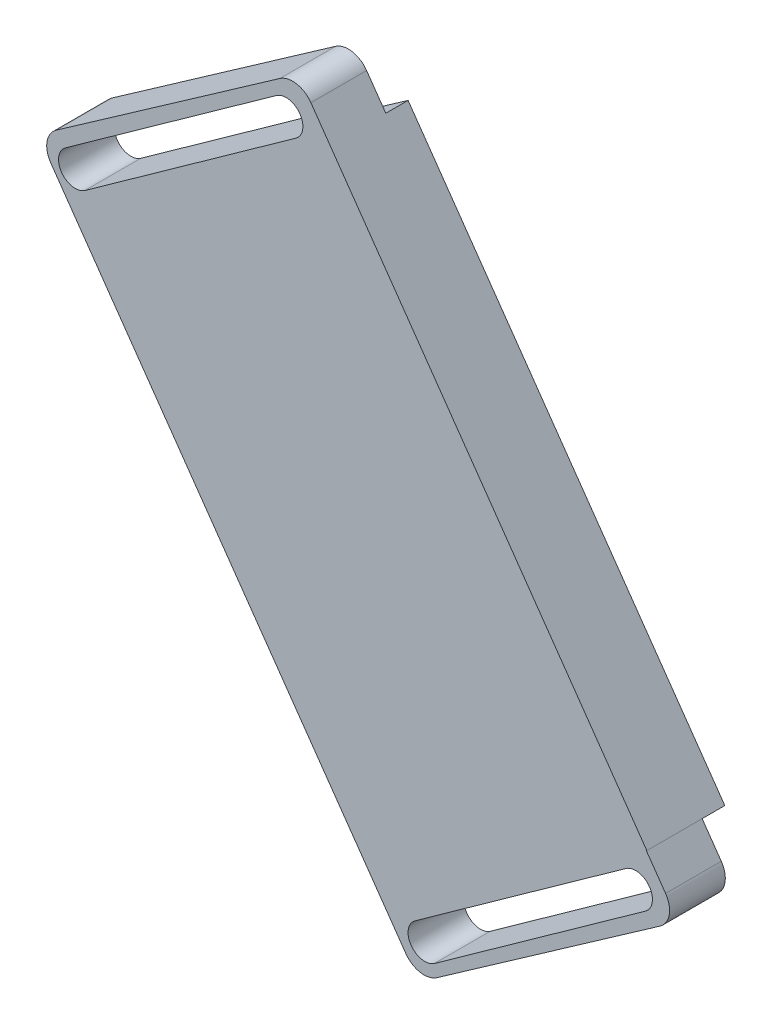
SolidWorks part; units mm, degrees
ref_plane "Piano frontale" through (0, 0, 0) normal (0, 0, 1) x (1, 0, 0)
ref_plane "Piano superiore" through (0, 0, 0) normal (0, 1, 0) x (1, 0, 0)
ref_plane "Piano destro" through (0, 0, 0) normal (1, 0, 0) x (0, 0, -1)
sketch "Schizzo1" plane through (0, 0, 0) normal (0, 0, 1) x (1, 0, 0)
  line L0 (-15.9091, 13.6426) -> (-5.6697, 20.8123)
  line L1 (-15.9091, 13.6426) -> (12.5116, -26.9464)
  line L2 (12.5116, -26.9464) -> (22.751, -19.7767)
  line L3 (-5.6697, 20.8123) -> (22.751, -19.7767)
  line L4 (-15.9091, 13.6426) -> (22.751, -19.7767) construction
  line L5 (12.5116, -26.9464) -> (-5.6697, 20.8123) construction
  line L6 (-6.5469, 19.0139) -> (20.7611, -19.9859)
  line L7 (-6.5469, 19.0139) -> (-13.9192, 13.8518)
  line L8 (-13.9192, 13.8518) -> (13.3888, -25.1481)
  line L9 (20.7611, -19.9859) -> (13.3888, -25.1481)
  line L10 (-6.5469, 19.0139) -> (13.3888, -25.1481) construction
  line L11 (-13.9192, 13.8518) -> (20.7611, -19.9859) construction
  line L12 (13.3888, -25.1481) -> (20.7611, -19.9859)
  line L13 (13.3888, -25.1481) -> (-13.9192, 13.8518)
  line L14 (20.7611, -19.9859) -> (-6.5469, 19.0139)
  line L15 (-13.9192, 13.8518) -> (-6.5469, 19.0139)
  line L16 (13.2898, -26.2909) -> (13.2041, -26.1685)
  line L17 (-15.1309, 14.2981) -> (-14.9919, 14.0995)
  line L18 (-14.9919, 14.0995) -> (-15.811, 13.526)
  line L19 (13.2041, -26.1685) -> (12.385, -26.7421)
  line L20 (-14.9919, 14.0995) -> (13.2041, -26.1685)
  line L21 (-14.9919, 14.0995) -> (-14.5004, 14.4437)
  line L22 (13.2041, -26.1685) -> (13.6956, -25.8244)
  line L23 (-14.5004, 14.4437) -> (13.6956, -25.8244)
  line L24 (-6.5298, 20.3206) -> (-6.3667, 20.0876)
  line L26 (21.8909, -20.2683) -> (21.7964, -20.1334)
  line L27 (21.7964, -20.1334) -> (22.6155, -19.5598)
  line L28 (-6.3667, 20.0876) -> (21.7964, -20.1334)
  line L29 (-6.3667, 20.0876) -> (-6.8582, 19.7435)
  line L30 (21.7964, -20.1334) -> (21.3049, -20.4775)
  line L31 (-6.8582, 19.7435) -> (21.3049, -20.4775)
  point P4 (0, 0)
  point P5 (3.421, -3.0671)
  point P10 (0, 0)
  point P11 (0, 0)
extrude "Estrusione-Estrusione1" add sketch "Schizzo1" along normal blind 7 contours L0 L3 L2 L1
extrude "Taglio-Estrusione1" cut sketch "Schizzo1<3>" along normal blind 6 contours L23 L21 L20 L22 | L29 L31 L30 L28 region at (-0.6481, -5.8624, 0) region at (7.4691, -0.195, 0)
sketch "Schizzo1<3>" plane through (0, 0, 0) normal (0, 0, 1) x (1, 0, 0) same geometry as "Schizzo1"
sketch "Schizzo3" plane through (16.7769, -23.9598, 0) normal (0.5736, -0.8192, 0) x (-0.8192, -0.5736, 0)
  line L1 (-7.2931, -7) -> (-23.2931, -7)
  line L2 (-7.2931, -7) -> (-7.2931, 0)
  line L3 (-7.2931, 0) -> (-23.2931, 0)
  line L4 (-23.2931, -7) -> (-23.2931, 0)
  line L5 (-7.2931, -7) -> (-23.2931, 0) construction
  line L6 (-7.2931, 0) -> (-23.2931, -7) construction
  point P4 (-15.2931, -3.5)
extrude "Estrusione-Estrusione2" add sketch "Schizzo3" against normal up to vertex (49.55 mm away) up to point (-5.6697, 20.8123, 7)
sketch "Schizzo6" plane through (16.7769, -23.9598, 0) normal (0.5736, -0.8192, 0) x (-0.8192, -0.5736, 0)
  line L1 (5.2069, -7) -> (-23.2458, -7)
  line L3 (5.2069, -2) -> (-23.2458, -2)
  line L5 (-23.2458, -2) -> (-23.2458, -7)
  line L6 (5.2069, -2) -> (5.2069, -7)
extrude "Estrusione-Estrusione5" add sketch "Schizzo6" along normal blind 5
sketch "Schizzo7" plane through (-11.6439, 16.6291, 0) normal (-0.5736, 0.8192, 0) x (0.8192, 0.5736, 0)
  line L0 (23.2931, 0) -> (23.2931, -7) construction
  line L1 (-5.2069, -7) -> (23.2931, -7)
  line L3 (-5.2069, -2) -> (23.2931, -2)
  line L5 (23.2931, -2) -> (23.2931, -7)
  line L8 (-5.2069, -7) -> (-5.2069, -2)
  point P4 (9.0431, -5.25)
extrude "Estrusione-Estrusione6" add sketch "Schizzo7" along normal blind 5
sketch "Schizzo8" plane through (0, 0, 2) normal (0, 0, -1) x (-1, 0, 0)
  line L0 (-34.8611, -14.1441) -> (-15.9349, -27.6725) construction
  line L1 (-33.9888, -12.9238) -> (-15.0626, -26.4522)
  line L2 (-35.7333, -15.3644) -> (-16.8072, -28.8928)
  line L3 (-3.4964, 30.2393) -> (15.4297, 16.7108) construction
  line L4 (-2.6242, 31.4596) -> (16.302, 17.9311)
  line L5 (-4.3687, 29.019) -> (14.5574, 15.4905)
  arc A0 (-33.9888, -12.9238) -> (-35.7333, -15.3644) centre (-34.8611, -14.1441) ccw
  arc A1 (-16.8072, -28.8928) -> (-15.0626, -26.4522) centre (-15.9349, -27.6725) ccw
  arc A2 (-2.6242, 31.4596) -> (-4.3687, 29.019) centre (-3.4964, 30.2393) ccw
  arc A3 (14.5574, 15.4905) -> (16.302, 17.9311) centre (15.4297, 16.7108) ccw
  point P2 (-25.398, -20.9083)
  point P9 (5.9666, 23.475)
extrude "Taglio-Estrusione8" cut sketch "Schizzo8" against normal through all both and the other way through all
fillet "Raccordo1" radius 2 4 edges at (-18.777, 17.7383, 4.5) (4.5688, 34.0853, 4.5) (15.3795, -31.0422, 4.5) (38.6866, -14.7224, 4.5)
